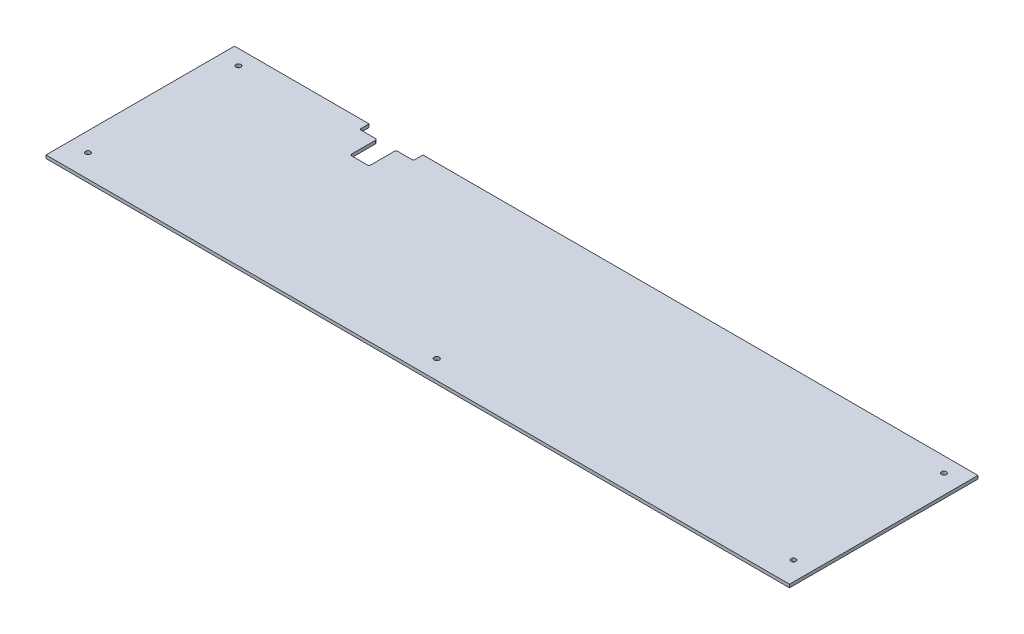
SolidWorks part; units mm, degrees
ref_plane "Alzado" through (0, 0, 0) normal (0, 0, 1) x (1, 0, 0)
ref_plane "Planta" through (0, 0, 0) normal (0, 1, 0) x (1, 0, 0)
ref_plane "Vista lateral" through (0, 0, 0) normal (1, 0, 0) x (0, 0, -1)
sketch "Croquis1" plane through (0, 0, 0) normal (0, 1, 0) x (1, 0, 0)
  line L0 (235.25, 120) -> (235.25, 0) construction
  line L1 (0, 0) -> (470.5, 0)
  line L2 (0, 0) -> (0, 120)
  line L3 (0, 120) -> (470.5, 120)
  line L4 (470.5, 0) -> (470.5, 120)
  line L5 (0, 60) -> (470.5, 60) construction
  circle A0 centre (12.5, 15) radius 1.55
  circle A1 centre (12.5, 110) radius 1.55
  circle A2 centre (458, 15) radius 1.55
  circle A3 centre (458, 110) radius 1.55
  dimension "D3" = 3.1
  dimension "D1" = 120
  dimension "D2" = 470.5
  dimension "D4" = 15
  dimension "D5" = 12.5
  dimension "D6" = 12.5
  dimension "D7" = 10
extrude "Saliente-Extruir1" add sketch "Croquis1" along normal blind 2
sketch "Croquis2" plane through (0, 0, 0) normal (0, -1, 0) x (1, 0, 0)
  line L0 (470, -0.5) -> (0.5, -0.5)
  line L1 (0.5, -0.5) -> (0.5, -119.5)
  line L2 (0.5, -119.5) -> (470, -119.5)
  line L3 (470, -119.5) -> (470, -0.5)
  line L4 (0, 0) -> (0, -120)
  line L5 (0, -120) -> (470.5, -120)
  line L6 (470.5, -120) -> (470.5, 0)
  line L7 (470.5, 0) -> (0, 0)
  line L8 (0, 0) -> (0, -120)
  line L9 (0, -120) -> (470.5, -120)
  line L10 (470.5, -120) -> (470.5, 0)
  line L11 (470.5, 0) -> (0, 0)
  dimension "D1" = 0
  dimension "D2" = 0.5
extrude "Cortar-Extruir1" cut sketch "Croquis2" against normal up to surface (2 mm away) up to face at (235.25, 2, -60)
sketch "Croquis3" plane through (0, 0, 0) normal (0, -1, 0) x (1, 0, 0)
  line L0 (0.5, -119.5) -> (470, -119.5) construction
  line L1 (85.5, -119.5) -> (119.5, -119.5)
  line L2 (85.5, -119.5) -> (85.5, -113.5)
  line L3 (85.5, -113.5) -> (96.5, -113.5)
  line L4 (119.5, -119.5) -> (119.5, -113.5)
  line L5 (108.5, -113.5) -> (119.5, -113.5)
  line L7 (96.5, -113.5) -> (96.5, -96.5)
  line L8 (96.5, -96.5) -> (108.5, -96.5)
  line L9 (108.5, -113.5) -> (108.5, -96.5)
  dimension "D1" = 34
  dimension "D2" = 6
  dimension "D3" = 12
  dimension "D4" = 85
  dimension "D5" = 17
  dimension "12" = 11
extrude "Cortar-Extruir2" cut sketch "Croquis3" against normal up to surface (2 mm away) up to face at (458, 2, -111.55)
fillet "Redondeo1" radius 1 6 edges at (85.5, 1, -113.5) (119.5, 1, -113.5) (108.5, 1, -113.5) (96.5, 1, -113.5) (96.5, 1, -96.5) (108.5, 1, -96.5)
sketch "Croquis4" plane through (0, 0, 0) normal (0, -1, 0) x (1, 0, 0)
  line L0 (235.25, -0.5) -> (235.25, -119.5) construction
  line L1 (470, -0.5) -> (0.5, -0.5) construction
  line L2 (119.5, -119.5) -> (470, -119.5) construction
  circle A0 centre (235.25, -12.5) radius 1.6
  dimension "D1" = 3.2
  dimension "D2" = 12
extrude "Cortar-Extruir3" cut sketch "Croquis4" against normal up to surface (2 mm away) up to face at (458, 2, -111.55)
